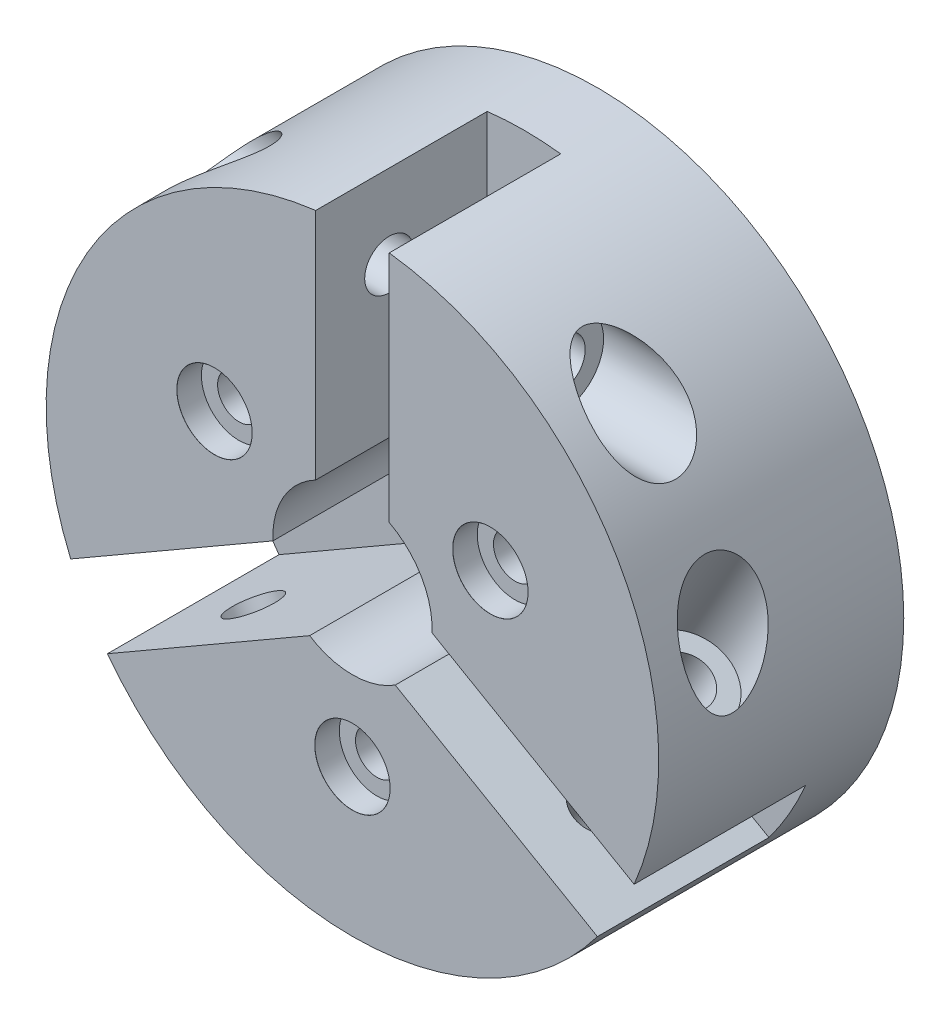
SolidWorks part; units mm, degrees
note: The reader was unsure of these and kept them because the rebuilt part matched: shared geometry of "Sketch2<6>", "Top Thru Hole Sketch<9>", "Sketch1<3>".
material "AISI 1045 Steel, cold drawn"
ref_plane "Front Plane" through (0, 0, 0) normal (0, 0, 1) x (1, 0, 0)
ref_plane "Top Plane" through (0, 0, 0) normal (0, 1, 0) x (1, 0, 0)
ref_plane "Right Plane" through (0, 0, 0) normal (1, 0, 0) x (0, 0, -1)
sketch "Base Sketch" plane through (0, 0, 0) normal (0, 0, 1) x (1, 0, 0)
  line L0 (0, 98.0607) -> (0, -98.0607) construction
  line L1 (-145.9753, 0) -> (145.9753, 0) construction
  line L2 (-92.7543, 53.5517) -> (92.7543, -53.5517) construction
  line L3 (75.2953, 43.4718) -> (-75.2953, -43.4718) construction
  circle A0 centre (0, 0) radius 125
  circle A1 centre (0, 0) radius 65 construction
  circle A2 centre (0, 0) radius 32.5
  point P6 (0, 0)
  point P9 (0, 0)
  point P10 (0, -65)
  point P11 (0, -65)
  point P14 (0, 0)
  point P15 (0, 0)
  point P19 (0, -65)
  point P20 (56.2917, 32.5)
  point P21 (-56.2917, 32.5)
  dimension "D1" = 250
  dimension "D2" = 130
  dimension "D5" = 30
  dimension "D3" = 65
  dimension "D4" = 30
extrude "Base Extrude" add sketch "Base Sketch" along normal blind 100 contours A0
sketch "Top Thru Hole Sketch" plane through (0, 0, 0) normal (1, 0, 0) x (0, 0, -1)
  line L0 (-100, 125) -> (-100, -125) construction
  line L1 (-100, 125) -> (-100, -125) construction
  line L2 (-70, 125) -> (-70, -125) construction
  line L3 (0, 125) -> (-100, 125) construction
  line L4 (-100, -125) -> (0, -125) construction
  line L5 (-100, 0) -> (0, 0) construction
  circle A0 centre (-70, 90) radius 17.5
  circle A2 centre (-70, 90) radius 10
  dimension "D2" = 90
  dimension "D3" = 35
  dimension "D4" = 20
  dimension "D1" = 30
extrude "Shank Hole Extruded Cut" cut sketch "Top Thru Hole Sketch" against normal through all both and the other way through all
ref_plane "Plane1" through (55, 0, 0) normal (1, 0, 0) x (0, 0, -1)
ref_plane "Plane2" through (-55, 0, 0) normal (1, 0, 0) x (0, 0, -1)
extrude "Outer Sleeve Extruded Cut" cut sketch "Sketch2<6>" against normal up to next from surface
sketch "Sketch2<6>" plane through (0, 0, 0) normal (1, 0, 0) x (0, 0, -1) same geometry as "Top Thru Hole Sketch"
extrude "Outer Sleeve Extruded Cut 2" cut sketch "Top Thru Hole Sketch<9>" along normal up to next from surface contours A0
sketch "Top Thru Hole Sketch<9>" plane through (0, 0, 0) normal (1, 0, 0) x (0, 0, -1) same geometry as "Top Thru Hole Sketch"
extrude "Slots Extruded Cut" cut sketch "Sketch1<3>" against normal blind 70 from surface at 100 contours A2 starting at face at (125, 0, 100)
sketch "Sketch1<3>" plane through (0, 0, 0) normal (0, 0, 1) x (1, 0, 0) same geometry as "Base Sketch"
sketch "Sketch11" plane through (0, 0, 0) normal (0, 1, 0) x (1, 0, 0)
  line L0 (0, -100) -> (0, 0) construction
  line L1 (0, -100) -> (0, 0) construction
  line L3 (-15, -30) -> (15, -30)
  line L4 (-15, -30) -> (-15, -100)
  line L5 (-15, -100) -> (15, -100)
  line L6 (15, -30) -> (15, -100)
  line L12 (-125, -100) -> (125, -100) construction
  point P10 (0, -30)
  dimension "D1" = 70
  dimension "D2" = 30
extrude "Front Slot Extruded Cut" cut sketch "Sketch11" against normal up to next from surface
pattern_circular "Circular Jaw Pattern" count 3 over 360 about axis through (0, 0, 0) along (0, 0, 1) of "Front Slot Extruded Cut"
pattern_circular "Counterbored Hole Circular Pattern" count 3 over 360 about axis through (0, 0, 0) along (0, 0, 1) of "Outer Sleeve Extruded Cut 2", "Outer Sleeve Extruded Cut", "Shank Hole Extruded Cut"
hole_wizard "CBORE for M16 Hex Head Bolt1" positions "Sketch16" profile "Sketch15" counterbore size "M16" standard "BSI" end condition through all
sketch "Sketch16" plane through (0, 0, 100) normal (0, 0, 1) x (1, 0, 0)
  point P0 (56.2917, 32.5)
  point P3 (0, -65)
  point P6 (-56.2917, 32.5)
sketch "Sketch15" plane through (56.2917, 32.5, 100) normal (1, 0, 0) x (0, -1, 0)
  line L0 (0, 0) -> (0, 100)
  line L1 (0, 100) -> (8.75, 100)
  line L3 (8.75, 100) -> (8.75, 10)
  line L4 (15.3565, 10) -> (8.75, 10)
  line L5 (15.3565, 10) -> (15.3565, 0.021)
  line L6 (15.3565, 0.021) -> (15.3815, 0)
  line L7 (15.3815, 0) -> (0, 0)
  line L8 (-15.3565, 0.021) -> (-15.3815, 0) construction
  line L11 (0, -6.35) -> (0, 107.95) construction
  dimension "Thru Hole Dia." = 17.5
  dimension "Thru Hole Depth" = 100
  dimension "C'Bore Dia." = 30.713
  dimension "C'Bore Depth" = 10
  dimension "Near C'Sink Dia." = 30.763
  dimension "Near C'Sink Angle" = 100
